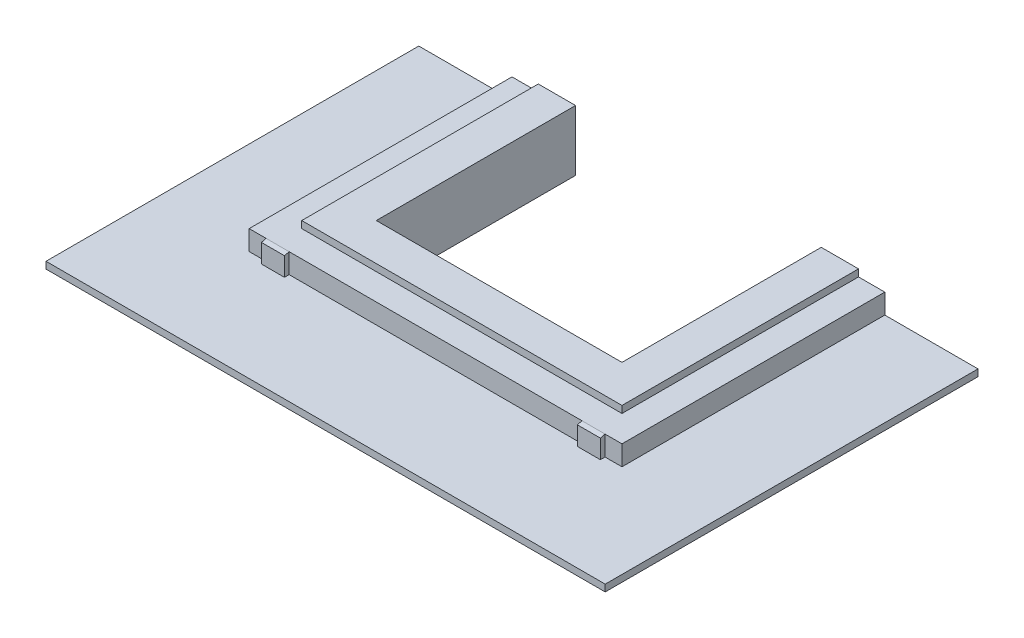
SolidWorks part; units mm, degrees
ref_plane "Top Plane" through (0, 0, 0) normal (0, 0, 1) x (1, 0, 0)
ref_plane "Front Plane" through (0, 0, 0) normal (0, 1, 0) x (1, 0, 0)
ref_plane "Right Plane" through (0, 0, 0) normal (1, 0, 0) x (0, 0, -1)
sketch "Sketch1" plane through (0, 0, 0) normal (0, 0, 1) x (1, 0, 0)
  line L1 (-2, -0.325) -> (2, -0.325)
  line L2 (-2, -0.325) -> (-2, 0.325)
  line L3 (-2, 0.325) -> (2, 0.325)
  line L4 (2, -0.325) -> (2, 0.325)
  line L5 (-2, -0.325) -> (2, 0.325) construction
  line L6 (-2, 0.325) -> (2, -0.325) construction
  point P0 (0, 0)
  dimension "D1" = 0.65
  dimension "D2" = 4
extrude "Boss-Extrude1" add sketch "Sketch1" along normal blind 2.82 contours L3 L4 L1 L2
sketch "Sketch2" plane through (0, -0.325, 0) normal (0, -1, 0) x (1, 0, 0)
  line L0 (-2, 0) -> (-1.718, 0)
  line L1 (-2, 0) -> (2, 0) construction
  line L2 (-1.718, 0) -> (-1.718, 2.538)
  line L3 (-1.718, 2.538) -> (1.718, 2.538)
  line L4 (1.718, 2.538) -> (1.718, 0)
  line L5 (1.718, 0) -> (2, 0)
  line L6 (2, 0) -> (2, 2.82)
  line L7 (2, 2.82) -> (-2, 2.82)
  line L8 (-2, 2.82) -> (-2, 0)
  dimension "D1" = 0.282
  dimension "D2" = 0.282
  dimension "D3" = 0.282
sketch "Sketch3" plane through (0, -0.325, 0) normal (0, -1, 0) x (1, 0, 0)
  line L0 (-2, 0) -> (2, 0) construction
  line L1 (-1.318, 0) -> (1.318, 0)
  line L2 (-1.318, 0) -> (-1.318, 2.138)
  line L3 (-1.318, 2.138) -> (1.318, 2.138)
  line L4 (1.318, 0) -> (1.318, 2.138)
  line L5 (-1.718, 0) -> (-1.718, 2.538) construction
  line L6 (-1.718, 2.538) -> (1.718, 2.538) construction
  line L7 (1.718, 2.538) -> (1.718, 0) construction
  dimension "D1" = 0.4
  dimension "D2" = 0.4
  dimension "D3" = 0.4
extrude "Cut-Extrude1" cut sketch "Sketch2" against normal blind 0.075 contours L3 L4 L5 L6 L7 L8 L0 L2
extrude "Cut-Extrude2" cut sketch "Sketch3" against normal through all contours L3 L4 L1 L2
ref_plane "Plane1" through (0, 0, 0) normal (0, -1, 0) x (-1, 0, 0)
mirror "Mirror1" about plane through (0, 0, 0) normal (0, -1, 0) of "Cut-Extrude1"
sketch "Sketch4" plane through (0, -0.25, 0) normal (0, -1, 0) x (1, 0, 0)
  line L0 (-1.788, 2.6805) -> (-1.718, 2.688)
  line L1 (-1.718, 2.688) -> (-1.648, 2.6805)
  line L2 (-1.648, 2.6805) -> (-1.648, 2.5955)
  line L3 (-1.648, 2.5955) -> (-1.718, 2.588)
  line L4 (-1.718, 2.588) -> (-1.788, 2.5955)
  line L5 (-1.788, 2.5955) -> (-1.788, 2.6805)
  line L6 (-1.788, 2.638) -> (-1.648, 2.638) construction
  line L7 (-1.718, 2.638) -> (-1.718, 2.538) construction
  line L8 (-0.926, 2.82) -> (-0.926, 2.538) construction
  line L9 (2, 2.82) -> (-2, 2.82) construction
  line L10 (-1.718, 2.538) -> (1.718, 2.538) construction
  line L11 (-2, 2.82) -> (-2, 0) construction
  line L12 (-0.996, 2.6805) -> (-0.996, 2.5955)
  line L13 (-0.996, 2.5955) -> (-0.926, 2.588)
  line L14 (-0.926, 2.588) -> (-0.856, 2.5955)
  line L15 (-0.856, 2.5955) -> (-0.856, 2.6805)
  line L16 (-0.856, 2.6805) -> (-0.926, 2.688)
  line L17 (-0.926, 2.688) -> (-0.996, 2.6805)
  line L18 (-0.996, 2.638) -> (-0.856, 2.638) construction
  dimension "D1" = 0.14
  dimension "D2" = 0.1
  dimension "D3" = 0.085
  dimension "D4" = 0.1
  dimension "D5" = 1.074
extrude "Boss-Extrude2" add sketch "Sketch4" along normal blind 0.025
mirror "Mirror2" about plane through (0, 0, 0) normal (1, 0, 0) of "Boss-Extrude2"
chamfer "Chamfer1" distance 0.01 angle 45 24 edges at (-1.683, -0.275, 2.5917) (-1.753, -0.275, 2.5917) (-1.788, -0.275, 2.638) (-1.648, -0.275, 2.638) (-1.683, -0.275, 2.6842) (-1.753, -0.275, 2.6842) (1.753, -0.275, 2.5917) (1.683, -0.275, 2.5917) (1.648, -0.275, 2.638) (1.683, -0.275, 2.6842) (1.753, -0.275, 2.6842) (1.788, -0.275, 2.638) (0.996, -0.275, 2.638) (0.961, -0.275, 2.5917) (0.891, -0.275, 2.5917) (0.856, -0.275, 2.638) (0.891, -0.275, 2.6842) (0.961, -0.275, 2.6842) (-0.996, -0.275, 2.638) (-0.961, -0.275, 2.5917) (-0.891, -0.275, 2.5917) (-0.856, -0.275, 2.638) (-0.891, -0.275, 2.6842) (-0.961, -0.275, 2.6842)
sketch "Sketch5" plane through (0, 0, 0) normal (1, 0, 0) x (0, 0, -1)
  line L0 (-2.538, -0.25) -> (-2.538, -0.1363) construction
  line L1 (-2.538, -0.1363) -> (-2.82, -0.1363) construction
  line L2 (-2.82, -0.25) -> (-2.82, 0.25) construction
  line L3 (-2.679, -0.1363) -> (-2.679, -0.6458) construction
  line L4 (-2.749, -0.25) -> (-2.7429, -0.32)
  line L5 (0, -0.25) -> (-2.82, -0.25) construction
  line L6 (-2.7429, -0.32) -> (-2.7304, -0.32)
  line L7 (-2.7304, -0.32) -> (-2.7304, -0.3736)
  line L8 (-2.679, -0.425) -> (-2.679, -0.25)
  line L9 (-2.6805, -0.25) -> (-2.5955, -0.25) construction
  line L10 (-2.679, -0.25) -> (-2.749, -0.25)
  line L11 (-2.679, -0.425) -> (-2.5953, -0.425) construction
  arc A0 (-2.7304, -0.3736) -> (-2.679, -0.425) centre (-2.679, -0.3736) ccw
  point P7 (-2.679, -0.1363)
  dimension "D1" = 0.175
  dimension "D2" = 0.07
  dimension "D3" = 0.1028
  dimension "D4" = 0.14
  dimension "D5" = 5
revolve "Revolve1" add sketch "Sketch5" angle 360 about L3
ref_plane "Plane2" through (-1.518, 0, 0) normal (-1, 0, 0) x (0, 0, 1)
sketch "Sketch6" plane through (-1.518, 0, 0) normal (-1, 0, 0) x (0, 0, 1)
  line L0 (2.338, 0.6914) -> (2.338, -1.1608) construction
  line L1 (2.538, -0.2875) -> (2.138, -0.2875) construction
  line L2 (2.538, -0.25) -> (2.538, -0.325) construction
  line L3 (2.138, 0.325) -> (2.138, -0.325) construction
  line L4 (2.488, -0.325) -> (2.4819, -0.395)
  line L5 (0, -0.325) -> (2.538, -0.325) construction
  line L6 (2.4819, -0.395) -> (2.423, -0.395)
  line L7 (2.253, -0.395) -> (2.1941, -0.395) construction
  line L8 (2.1941, -0.395) -> (2.188, -0.325) construction
  line L9 (2.188, -0.325) -> (2.488, -0.325) construction
  line L10 (2.488, -0.325) -> (2.338, -0.325)
  line L11 (2.338, -0.325) -> (2.338, -0.555)
  arc A0 (2.423, -0.395) -> (2.253, -0.395) centre (2.338, -0.4524) cw construction
  arc A1 (2.338, -0.555) -> (2.423, -0.395) centre (2.338, -0.4524) ccw
  point P8 (2.338, -0.2875)
  point P16 (2.338, -0.325)
  point P19 (2.338, -0.555)
  dimension "D1" = 0.07
  dimension "D2" = 0.17
  dimension "D3" = 0.23
  dimension "D4" = 5
  dimension "D5" = 0.3
revolve "Revolve2" add sketch "Sketch6" angle 360 about L11
sketch "Sketch7" plane through (-2, 0, 0) normal (-1, 0, 0) x (0, 0, 1)
  line L0 (2.82, -0.25) -> (2.487, -1.1648)
  line L1 (2.82, -0.25) -> (2.82, 0.25) construction
  dimension "D1" = 20
ref_plane "Plane3" through (0, 0.2555, 0.093) normal (0, -0.9397, -0.342) x (-1, 0, 0)
sketch "Sketch8" plane through (0, 0.2555, 0.093) normal (0, -0.9397, -0.342) x (-1, 0, 0)
  line L1 (1.3355, -2.1096) -> (1.7755, -2.1096)
  line L2 (1.3355, -2.1096) -> (1.3355, -2.6826)
  line L3 (1.3355, -2.6826) -> (1.7755, -2.6826)
  line L4 (1.7755, -2.1096) -> (1.7755, -2.6826)
extrude "Cut-Extrude3" cut sketch "Sketch8" against normal blind 0.04
mirror "Mirror3" about plane through (0, 0, 0) normal (1, 0, 0) of "Cut-Extrude3", "Revolve2"
sketch "Sketch9" plane through (0, -0.325, 0) normal (0, -1, 0) x (1, 0, 0)
  line L0 (0, 2.1825) -> (0, 2.138) construction
  line L1 (-0.2925, 2.4935) -> (0.2925, 2.4935)
  line L2 (-0.2925, 2.4935) -> (-0.2925, 2.1825)
  line L3 (-0.2925, 2.1825) -> (0.2925, 2.1825)
  line L4 (0.2925, 2.4935) -> (0.2925, 2.1825)
  line L5 (-1.318, 2.138) -> (1.318, 2.138) construction
  line L6 (0.2925, 2.338) -> (0.5053, 2.338) construction
  line L7 (0.5053, 2.338) -> (0.5053, 2.538) construction
  line L8 (-1.718, 2.538) -> (1.718, 2.538) construction
  line L9 (0.5053, 2.338) -> (0.5053, 2.138) construction
  dimension "D1" = 0.585
  dimension "D2" = 0.311
extrude "Boss-Extrude3" add sketch "Sketch9" along normal blind 0.07
chamfer "Chamfer2" distance 0.07 angle 5 4 edges at (0, -0.395, 2.4935) (0.2925, -0.395, 2.338) (0, -0.395, 2.1825) (-0.2925, -0.395, 2.338) first distance on face at (0, -0.36, 2.4935) first distance on face at (0.2925, -0.36, 2.338) first distance on face at (0, -0.36, 2.1825) first distance on face at (-0.2925, -0.36, 2.338)
sketch "Sketch10" plane through (0, -0.395, 0) normal (0, -1, 0) x (1, 0, 0)
  line L0 (-0.2925, 2.1825) -> (0.2925, 2.1825) construction
  line L1 (-0.142, 2.3865) -> (0.142, 2.3865)
  line L2 (-0.142, 2.3865) -> (-0.142, 2.2465)
  line L3 (-0.142, 2.2465) -> (0.142, 2.2465)
  line L4 (0.142, 2.3865) -> (0.142, 2.2465)
  line L5 (0, 2.3865) -> (0, 2.4874) construction
  line L6 (0.2864, 2.4874) -> (-0.2864, 2.4874) construction
  dimension "D1" = 0.284
  dimension "D2" = 0.14
  dimension "D3" = 0.064
extrude "Cut-Extrude4" cut sketch "Sketch10" against normal blind 0.01
chamfer "Chamfer3" distance 0.01 angle 45 4 edges at (0, -0.385, 2.3865) (0.142, -0.385, 2.3165) (0, -0.385, 2.2465) (-0.142, -0.385, 2.3165)
sketch "Sketch11" plane through (0, -0.395, 0) normal (0, -1, 0) x (1, 0, 0)
  line L0 (0.2864, 2.4874) -> (-0.2864, 2.4874) construction
  line L1 (-0.142, 2.3865) -> (0.142, 2.3865)
  line L2 (-0.142, 2.3865) -> (-0.142, 2.4874)
  line L3 (-0.142, 2.4874) -> (0.142, 2.4874)
  line L4 (0.142, 2.3865) -> (0.142, 2.4874)
  line L5 (0.142, 2.2465) -> (0.142, 2.3865) construction
extrude "Boss-Extrude4" add sketch "Sketch11" along normal blind 0.05
sketch "Sketch12" plane through (0.142, 0, 0) normal (1, 0, 0) x (0, 0, -1)
  line L0 (-2.4874, -0.445) -> (-2.4874, -0.395)
  line L1 (-2.4874, -0.395) -> (-2.4186, -0.445)
  line L2 (-2.4874, -0.445) -> (-2.4186, -0.445)
  line L3 (-2.3865, -0.395) -> (-2.4105, -0.445)
  line L4 (-2.3865, -0.445) -> (-2.4874, -0.445) construction
  line L5 (-2.4105, -0.445) -> (-2.3865, -0.445)
  line L6 (-2.3865, -0.445) -> (-2.3865, -0.395)
extrude "Cut-Extrude5" cut sketch "Sketch12" against normal up to next
sketch "Sketch13" plane through (0, -0.219, 2.5028) normal (0, -0.0872, 0.9962) x (1, 0, 0)
  line L0 (-0.142, -0.1977) -> (-0.1264, -0.2332)
  line L2 (-0.1264, -0.2332) -> (-0.142, -0.2332)
  line L3 (-0.142, -0.2332) -> (-0.142, -0.1977)
  line L4 (0.142, -0.1977) -> (0.1264, -0.2332)
  line L5 (0.1264, -0.2332) -> (0.142, -0.2332)
  line L6 (0.142, -0.2332) -> (0.142, -0.1977)
  line L7 (-0.142, -0.2332) -> (0.142, -0.2332) construction
extrude "Cut-Extrude6" cut sketch "Sketch13" against normal up to next
sketch "Sketch14" plane through (0, 0, 2.82) normal (0, 0, 1) x (1, 0, 0)
  line L0 (2, -0.25) -> (-2, -0.25) construction
  line L1 (-1.8182, -0.25) -> (-1.5713, -0.25)
  line L2 (-1.8182, -0.25) -> (-1.8182, 0.25)
  line L3 (-1.8182, 0.25) -> (-1.5713, 0.25)
  line L4 (-1.5713, -0.25) -> (-1.5713, 0.25)
  line L5 (2, 0.25) -> (-2, 0.25) construction
extrude "Boss-Extrude5" add sketch "Sketch14" along normal blind 0.05
chamfer "Chamfer4" distance 0.05 angle 14 2 edges at (-1.6948, 0.25, 2.87) (-1.6948, -0.25, 2.87) first distance on face at (-0.5649, 0.25, 1.8413) first distance on face at (0, -0.25, 2.749)
mirror "Mirror4" about plane through (0, 0, 0) normal (1, 0, 0) of "Chamfer4", "Boss-Extrude5"
sketch "Sketch15" plane through (0, -0.25, 0) normal (0, -1, 0) x (1, 0, 0)
  line L0 (-3, 0) -> (-1.318, 0)
  line L1 (-3, 0) -> (3, 0) construction
  line L2 (-3, 0) -> (-3, 4)
  line L3 (-3, 4) -> (3, 4)
  line L4 (3, 0) -> (3, 4)
  line L5 (-1.318, 0) -> (-1.318, 2.138)
  line L6 (-1.318, 2.138) -> (1.318, 2.138)
  line L7 (1.318, 2.138) -> (1.318, 0)
  line L8 (1.318, 0) -> (3, 0)
  dimension "D1" = 4
  dimension "D2" = 6
ref_plane "Plane4" through (0, 0, 0) normal (0, -1, 0) x (-1, 0, 0)
extrude "Boss-Extrude6" add sketch "Sketch15" along normal mid plane 0.0729 from surface contours L3 L4 L8 L7 L6 L5 L0 L2 starting at plane "Plane4"
